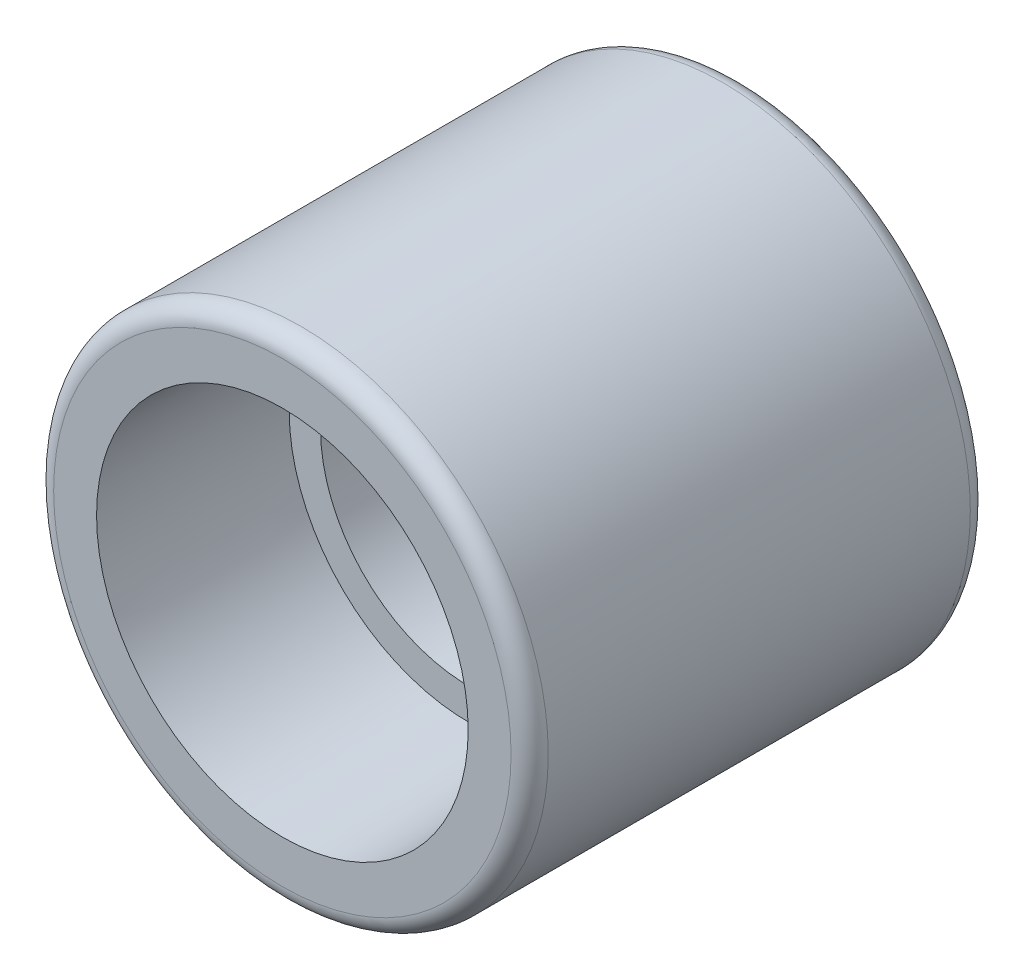
SolidWorks part; units mm, degrees
extrude "Body" add sketch "BodySch" along normal blind 41.275
sketch "BodySch" plane through (0, 0, 0) normal (0, 0, 1) x (1, 0, 0)
  circle A0 centre (0, 0) radius 22.225
  dimension "Dia" = 44.45
material "PW90:Mi:0:191:Ar:0:-1:C1:1:2:3:Re:17:Ts:18:19:20:21:22:23:"
ref_plane "Front" through (0, 0, 0) normal (0, 0, 1) x (1, 0, 0)
ref_plane "Top" through (0, 0, 0) normal (0, 1, 0) x (1, 0, 0)
ref_plane "Right" through (0, 0, 0) normal (1, 0, 0) x (0, 0, -1)
sketch "FlowSch" plane through (0, 0, 41.275) normal (0, 0, 1) x (1, 0, 0)
  circle A0 centre (0, 0) radius 13.3604
  dimension "Dia" = 26.7208
extrude "Flow" cut sketch "FlowSch" against normal blind 31.75
sketch "ThreadSch" plane through (0, 0, 0) normal (1, 0, 0) x (0, 0, -1)
  line L0 (0, 0) -> (-41.275, 0) construction
  line L1 (-41.275, 0) -> (0, 0) construction
  line L2 (-24.4856, 0) -> (-24.4856, 16.1778)
  line L3 (-24.4856, 16.1778) -> (-41.275, 16.7005)
  line L4 (-41.275, 16.7005) -> (-41.275, 0)
  line L5 (-41.275, 0) -> (-24.4856, 0)
  line L6 (-41.275, 22.225) -> (-41.275, -22.225) construction
  dimension "D1" = 1.783
  dimension "Dia" = 33.401
revolve "Thread" cut sketch "ThreadSch" angle 360 about L0
fillet "Fillet1" radius 1.67 2 edges at (22.225, 0, 41.275) (22.225, 0, 0)
sketch "CPointSketch" plane through (0, 0, 24.4856) normal (0, 0, 1) x (1, 0, 0)
  circle A0 centre (0, 0) radius 16.1778 construction
  circle A1 centre (0, 0) radius 16.1778
other "CPoint1" parameters "Diameter"=25.4, "StubLength"=0
ref_axis "Axis1" through (0, 0, 34.4856) along (0, 0, -1)
equation "\"EdgeRadius@Fillet1\" =  ( \"Dia@ThreadSch\" - \"Dia@FlowSch\" )  / 4"
